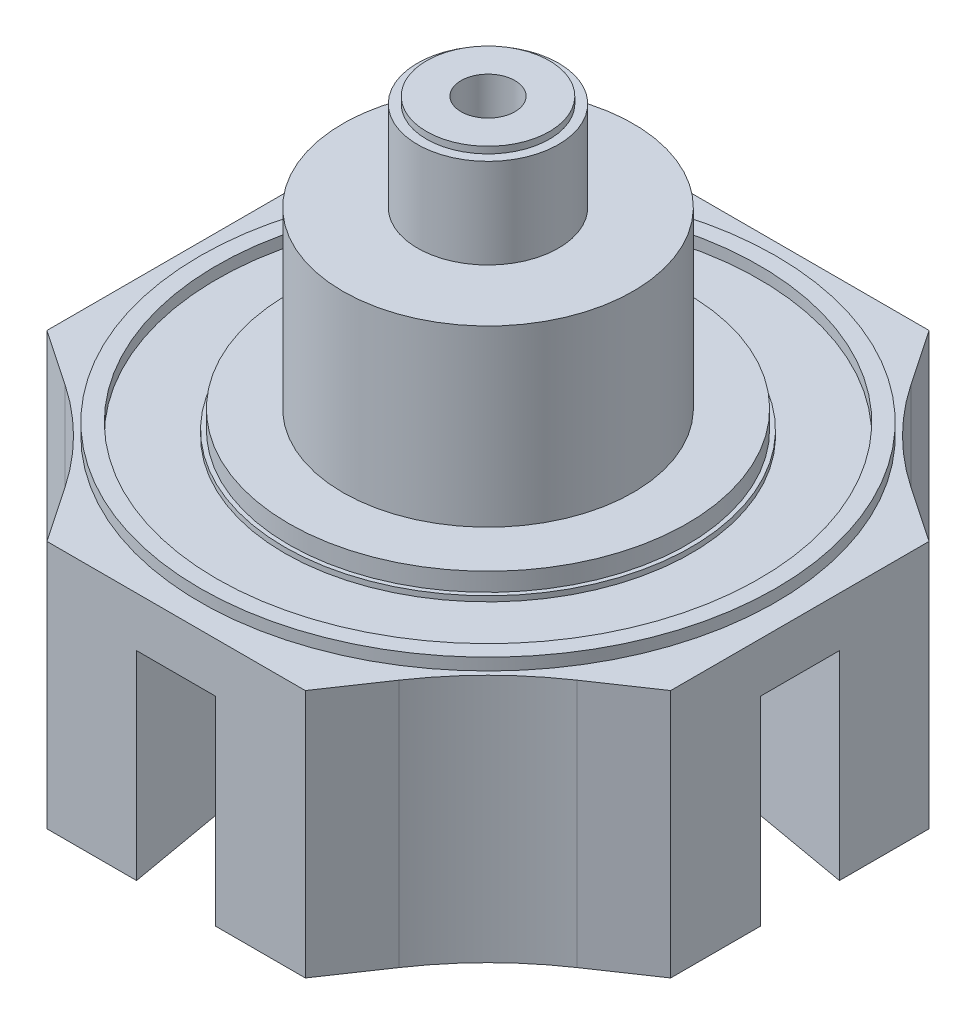
SolidWorks part; units mm, degrees
ref_plane "Front Plane" through (0, 0, 0) normal (0, 0, 1) x (1, 0, 0)
ref_plane "Top Plane" through (0, 0, 0) normal (0, 1, 0) x (1, 0, 0)
ref_plane "Right Plane" through (0, 0, 0) normal (1, 0, 0) x (0, 0, -1)
sketch "Sketch1" plane through (0, 0, 0) normal (0, 1, 0) x (1, 0, 0)
  line L0 (-19.7716, -47.7327) -> (-47.7327, -19.7716) construction
  line L1 (-47.7327, -19.7716) -> (-47.7327, 19.7716)
  line L2 (-47.7327, 19.7716) -> (-19.7716, 47.7327) construction
  line L3 (-19.7716, 47.7327) -> (19.7716, 47.7327)
  line L4 (19.7716, 47.7327) -> (47.7327, 19.7716) construction
  line L5 (47.7327, 19.7716) -> (47.7327, -19.7716)
  line L6 (47.7327, -19.7716) -> (19.7716, -47.7327) construction
  line L7 (19.7716, -47.7327) -> (-19.7716, -47.7327)
  line L8 (-47.7327, -19.7716) -> (-31.0581, -31.0581)
  line L9 (-31.0581, -31.0581) -> (-19.7716, -47.7327)
  line L10 (-13.992, 0) -> (18.484, 0) construction
  line L11 (0, -11.0907) -> (0, 17.8248) construction
  line L12 (-31.0581, 31.0581) -> (-19.7716, 47.7327)
  line L13 (-47.7327, 19.7716) -> (-31.0581, 31.0581)
  line L14 (31.0581, -31.0581) -> (19.7716, -47.7327)
  line L15 (47.7327, -19.7716) -> (31.0581, -31.0581)
  line L16 (31.0581, 31.0581) -> (19.7716, 47.7327)
  line L17 (47.7327, 19.7716) -> (31.0581, 31.0581)
  circle A0 centre (0, 0) radius 47.7327 construction
  point P13 (33.7521, -33.7521)
  point P14 (0, 47.7327)
  point P15 (-33.7521, 33.7521)
  point P16 (33.7521, 33.7521)
  point P17 (47.7327, 0)
  point P19 (-47.7327, 0)
  point P21 (-33.7521, -33.7521)
  point P28 (0, -47.7327)
  dimension "D1" = 39.5431
  dimension "D2" = 3.81
extrude "Base" add sketch "Sketch1" along normal blind 38.1
sketch "Sketch2" plane through (0, 0, 0) normal (0, -1, 0) x (1, 0, 0)
  line L0 (6.0556, -47.7327) -> (-6.0556, -47.7327)
  line L1 (19.7716, -47.7327) -> (-19.7716, -47.7327) construction
  line L2 (-6.0556, -47.7327) -> (-11.43, -17.2527)
  line L3 (-11.43, -17.2527) -> (11.43, -17.2527)
  line L4 (11.43, -17.2527) -> (6.0556, -47.7327)
  line L5 (-35.921, -35.921) -> (35.921, 35.921) construction
  line L6 (-35.921, 35.921) -> (35.921, -35.921) construction
  line L11 (-17.2527, -11.43) -> (-17.2527, 11.43)
  line L12 (-47.7327, -6.0556) -> (-17.2527, -11.43)
  line L13 (-47.7327, 6.0556) -> (-47.7327, -6.0556)
  line L14 (-17.2527, 11.43) -> (-47.7327, 6.0556)
  line L15 (17.2527, 11.43) -> (17.2527, -11.43)
  line L16 (47.7327, 6.0556) -> (17.2527, 11.43)
  line L17 (47.7327, -6.0556) -> (47.7327, 6.0556)
  line L18 (17.2527, -11.43) -> (47.7327, -6.0556)
  line L19 (6.0556, 47.7327) -> (11.43, 17.2527)
  line L20 (-6.0556, 47.7327) -> (6.0556, 47.7327)
  line L21 (-11.43, 17.2527) -> (-6.0556, 47.7327)
  line L22 (11.43, 17.2527) -> (-11.43, 17.2527)
  line L23 (31.0581, -31.0581) -> (19.7716, -47.7327) construction
  line L24 (47.7327, -19.7716) -> (31.0581, -31.0581) construction
  line L25 (31.0581, 31.0581) -> (47.7327, 19.7716) construction
  line L26 (19.7716, 47.7327) -> (31.0581, 31.0581) construction
  point P6 (0, -47.7327)
  point P7 (0, -47.7327)
  dimension "D1" = 80
  dimension "D2" = 80
  dimension "D3" = 30.48
  dimension "D4" = 22.86
extrude "Dovetail cuts" cut sketch "Sketch2" against normal blind 30.48
sketch "Sketch3" plane through (0, 38.1, 0) normal (0, 1, 0) x (1, 0, 0)
  circle A0 centre (0, 0) radius 31.115
  dimension "D1" = 62.23
extrude "Lower washer lip" add sketch "Sketch3" along normal blind 0.8128
sketch "Sketch4" plane through (0, 38.1, 0) normal (0, 1, 0) x (1, 0, 0)
  circle A0 centre (0, 0) radius 41.529
  circle A1 centre (0, 0) radius 44.069
  dimension "D1" = 83.058
  dimension "D2" = 88.138
extrude "Retaining lip" add sketch "Sketch4" along normal blind 1.8288
sketch "Sketch6" plane through (0, 38.9128, 0) normal (0, 1, 0) x (1, 0, 0)
  circle A0 centre (0, 0) radius 30.48
  dimension "D1" = 60.96
extrude "Upper bearing lip" add sketch "Sketch6" along normal blind 2.7972
sketch "Sketch7" plane through (0, 41.71, 0) normal (0, 1, 0) x (1, 0, 0)
  circle A0 centre (0, 0) radius 22.225
  dimension "D1" = 44.45
extrude "Central shaft" add sketch "Sketch7" along normal blind 26.67
sketch "Sketch5" plane through (0, 0, 0) normal (0, -1, 0) x (1, 0, 0)
  circle A0 centre (0, 0) radius 7.62
  dimension "D1" = 15.24
extrude "Nut clearance shaft" cut sketch "Sketch5" against normal blind 44.45
sketch "Sketch8" plane through (0, 68.38, 0) normal (0, 1, 0) x (1, 0, 0)
  circle A0 centre (0, 0) radius 10.795
  dimension "D1" = 21.59
extrude "Through Shaft" add sketch "Sketch8" along normal blind 14.7574
sketch "Sketch9" plane through (0, 83.1374, 0) normal (0, 1, 0) x (1, 0, 0)
  circle A0 centre (0, 0) radius 4.1275
  dimension "D1" = 8.255
extrude "Through Hole" cut sketch "Sketch9" against normal through all
sketch "Sketch10" plane through (0, 44.45, 0) normal (0, -1, 0) x (1, 0, 0)
  line L0 (3.2875, 5.694) -> (6.5749, 0)
  line L1 (6.5749, 0) -> (3.2875, -5.694)
  line L2 (3.2875, -5.694) -> (-3.2875, -5.694)
  line L3 (-3.2875, -5.694) -> (-6.5749, 0)
  line L4 (-6.5749, 0) -> (-3.2875, 5.694)
  line L5 (-3.2875, 5.694) -> (3.2875, 5.694)
  circle A0 centre (0, 0) radius 5.694 construction
  point P5 (0, 5.694)
  point P10 (4.9312, 2.847)
  point P11 (4.9312, -2.847)
  point P12 (0, -5.694)
  point P13 (-4.9312, 2.847)
  point P14 (-1.9947, -3.7117)
  point P15 (-2.3268, -3.6154)
  point P16 (1.4926, 2.8758)
  point P17 (-4.9312, -2.847)
  point P18 (-3.5309, 0)
  point P19 (0, 0)
  dimension "D1" = 11.3881
extrude "Nut slot" cut sketch "Sketch10" against normal blind 5.6007
sketch "Sketch11" plane through (0, 83.1374, 0) normal (0, 1, 0) x (1, 0, 0)
  circle A1 centre (0, 0) radius 9.398
  circle A2 centre (0, 0) radius 10.795 construction
  circle A3 centre (0, 0) radius 10.795
  dimension "D1" = 18.796
extrude "Upper washer lip" cut sketch "Sketch11" against normal blind 1.016
fillet "Fillet2" radius 50.8 4 edges at (-31.0581, 19.05, -31.0581) (31.0581, 19.05, -31.0581) (31.0581, 19.05, 31.0581) (-31.0581, 19.05, 31.0581)
